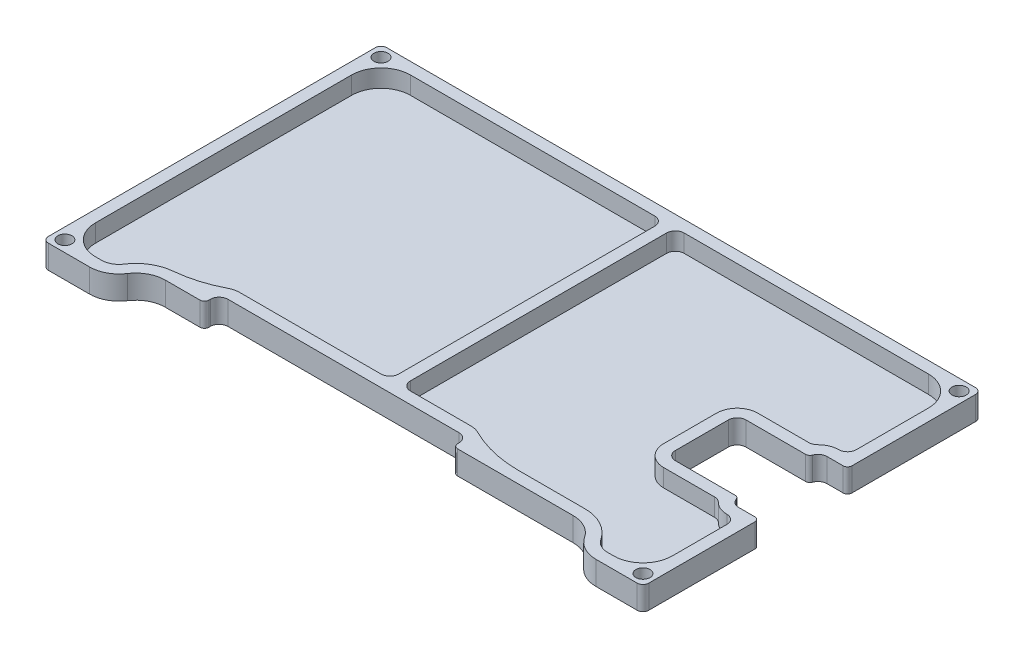
SolidWorks part; units mm, degrees
material "7075-T6 (SN)"
ref_plane "Ebene vorne" through (0, 0, 0) normal (0, 0, 1) x (1, 0, 0)
ref_plane "Ebene oben" through (0, 0, 0) normal (0, 1, 0) x (1, 0, 0)
ref_plane "Ebene rechts" through (0, 0, 0) normal (1, 0, 0) x (0, 0, -1)
sketch "Skizze1" plane through (0, 0, 0) normal (0, 1, 0) x (1, 0, 0)
  line L1 (-49.1, -26.85) -> (49.1, -26.85) construction
  line L2 (-49.1, -26.85) -> (-49.1, 26.85) construction
  line L3 (-49.1, 26.85) -> (49.1, 26.85) construction
  line L4 (49.1, -26.85) -> (49.1, 26.85) construction
  line L5 (-49.1, -26.85) -> (49.1, 26.85) construction
  line L6 (-49.1, 26.85) -> (49.1, -26.85) construction
  line L7 (-51, -28.75) -> (51, -28.75)
  line L8 (-51, -28.75) -> (-51, 28.75)
  line L9 (-51, 28.75) -> (51, 28.75)
  line L10 (51, -28.75) -> (51, 28.75)
  line L11 (-51, -28.75) -> (51, 28.75) construction
  line L12 (-51, 28.75) -> (51, -28.75) construction
  point P0 (0, 0)
  point P6 (0, 0)
  dimension "D1" = 102
  dimension "D2" = 57.5
  dimension "D3" = 98.2
  dimension "D4" = 53.7
extrude "Aufsatz-Linear austragen1" add sketch "Skizze1" along normal blind 1
fillet "Verrundung1" radius 1 4 edges at (51, 0.5, -28.75) (51, 0.5, 28.75) (-51, 0.5, 28.75) (-51, 0.5, -28.75)
sketch "Skizze5" plane through (0, 1, 0) normal (0, 1, 0) x (1, 0, 0)
  line L0 (-43, -28.75) -> (43, -28.75)
  line L1 (-50, -28.75) -> (50, -28.75) construction
  line L2 (-51, 27.75) -> (-51, -27.75) construction
  line L3 (34.6484, -24.25) -> (-34.6484, -24.25)
  line L4 (51, -27.75) -> (51, 27.75) construction
  arc A0 (-38.8242, -26.5) -> (-43, -28.75) centre (-43, -23.75) cw
  arc A1 (-38.8242, -26.5) -> (-34.6484, -24.25) centre (-34.6484, -29.25) cw
  arc A2 (38.8242, -26.5) -> (34.6484, -24.25) centre (34.6484, -29.25) ccw
  arc A3 (43, -28.75) -> (38.8242, -26.5) centre (43, -23.75) cw
  dimension "D3" = 5
  dimension "D1" = 8
  dimension "D2" = 8
  dimension "D4" = 4.5
extrude "Schnitt-Linear austragen1" cut sketch "Skizze5" against normal up to next
sketch "Skizze6" plane through (0, 1, 0) normal (0, 1, 0) x (1, 0, 0)
  line L0 (14.25, -21.75) -> (-28, -21.75)
  line L2 (-28, -21.75) -> (-28, -24.25)
  line L3 (-28, -24.25) -> (14.25, -24.25)
  line L4 (14.25, -24.25) -> (14.25, -21.75)
  line L5 (51, -27.75) -> (51, 27.75) construction
  line L7 (33.75, 4.5) -> (46, 4.5)
  line L8 (51, 4.5) -> (51, -7.5)
  line L9 (46, -7.5) -> (33.75, -7.5)
  line L10 (33.75, -7.5) -> (33.75, 4.5)
  line L11 (43, -28.75) -> (50, -28.75) construction
  line L12 (-51, 27.75) -> (-51, -27.75) construction
  line L13 (34.6484, -24.25) -> (-34.6484, -24.25) construction
  line L14 (46, -7.5) -> (46, -9)
  line L15 (46, -9) -> (51, -9)
  line L16 (51, -9) -> (51, -7.5)
  line L17 (46, 4.5) -> (46, 6)
  line L18 (46, 6) -> (51, 6)
  line L19 (51, 6) -> (51, 4.5)
  line L20 (46, -7.5) -> (51, -7.5) construction
  line L21 (46, 4.5) -> (51, 4.5) construction
  dimension "D1" = 42.25
  dimension "D2" = 23
  dimension "D3" = 2.5
  dimension "D4" = 21.25
  dimension "D5" = 12
  dimension "D6" = 17.25
  dimension "D7" = 15
  dimension "D8" = 5
extrude "Schnitt-Linear austragen2" cut sketch "Skizze6" against normal up to next
fillet "Verrundung2" radius 1.5 6 edges at (33.75, 0.5, -4.5) (33.75, 0.5, 7.5) (14.25, 0.5, 21.75) (-28, 0.5, 21.75) (46, 0.5, -6) (46, 0.5, 9)
fillet "Verrundung3" radius 0.75 6 edges at (-28, 0.5, 24.25) (14.25, 0.5, 24.25) (51, 0.5, -6) (51, 0.5, 9) (46, 0.5, -4.5) (46, 0.5, 7.5)
sketch "Skizze8" plane through (0, 1, 0) normal (0, 1, 0) x (1, 0, 0)
  line L0 (35.25, 6.5) -> (44.6277, 6.5)
  line L1 (47.5, 8) -> (49, 8)
  line L2 (49, 8) -> (49, 26.75)
  line L3 (49, 26.75) -> (1, 26.75)
  line L4 (-49, 26.75) -> (-49, -26.75)
  line L5 (-49, -26.75) -> (-43, -26.75)
  line L6 (-34.6484, -22.25) -> (-29.8541, -22.25)
  line L7 (-29.8541, -22.25) -> (-29.8541, -22.25)
  line L8 (-26.5, -19.75) -> (-1, -19.75)
  line L9 (16.1041, -22.25) -> (16.1041, -22.25)
  line L10 (16.1041, -22.25) -> (34.6484, -22.25)
  line L11 (43, -26.75) -> (49, -26.75)
  line L12 (49, -26.75) -> (49, -11)
  line L13 (49, -11) -> (47.5, -11)
  line L14 (44.6277, -9.5) -> (35.25, -9.5)
  line L15 (31.75, -6) -> (31.75, 3)
  line L16 (35.25, 4.5) -> (45.3787, 4.5)
  line L17 (47.5, 6) -> (50.25, 6)
  line L18 (51, 6.75) -> (51, 27.75)
  line L19 (50, 28.75) -> (-50, 28.75)
  line L20 (-51, 27.75) -> (-51, -27.75)
  line L21 (-50, -28.75) -> (-43, -28.75)
  line L22 (-34.6484, -24.25) -> (-28.75, -24.25)
  line L23 (-28, -23.5) -> (-28, -23.25)
  line L24 (-26.5, -21.75) -> (12.75, -21.75)
  line L25 (14.25, -23.25) -> (14.25, -23.5)
  line L26 (15, -24.25) -> (34.6484, -24.25)
  line L27 (43, -28.75) -> (50, -28.75)
  line L28 (51, -27.75) -> (51, -9.75)
  line L29 (50.25, -9) -> (47.5, -9)
  line L30 (45.3787, -7.5) -> (35.25, -7.5)
  line L31 (33.75, -6) -> (33.75, 3)
  line L32 (35.25, 4.5) -> (45.3787, 4.5)
  line L33 (47.5, 6) -> (50.25, 6)
  line L34 (51, 6.75) -> (51, 27.75)
  line L35 (50, 28.75) -> (-50, 28.75)
  line L36 (-51, 27.75) -> (-51, -27.75)
  line L37 (-50, -28.75) -> (-43, -28.75)
  line L38 (-34.6484, -24.25) -> (-28.75, -24.25)
  line L39 (-28, -23.5) -> (-28, -23.25)
  line L40 (-26.5, -21.75) -> (12.75, -21.75)
  line L41 (14.25, -23.25) -> (14.25, -23.5)
  line L42 (15, -24.25) -> (34.6484, -24.25)
  line L43 (43, -28.75) -> (50, -28.75)
  line L44 (51, -27.75) -> (51, -9.75)
  line L45 (50.25, -9) -> (47.5, -9)
  line L46 (45.3787, -7.5) -> (35.25, -7.5)
  line L47 (33.75, -6) -> (33.75, 3)
  line L48 (-1, 26.75) -> (-1, -19.75)
  line L49 (1, 0) -> (0, 0) construction
  line L50 (0, 0) -> (-1, 0) construction
  line L51 (1, 26.75) -> (1, -19.75)
  line L52 (1, -19.75) -> (12.75, -19.75)
  line L53 (-26.5, -19.75) -> (12.75, -19.75) construction
  line L54 (-1, 26.75) -> (-49, 26.75)
  line L55 (49, 26.75) -> (-49, 26.75) construction
  arc A0 (44.6277, 6.5) -> (44.6277, 6.5) centre (44.6277, 6.5) ccw
  arc A1 (47.5, 8) -> (44.6277, 6.5) centre (47.5, 4.5) ccw
  arc A2 (49, 8) -> (49, 8) centre (49, 8) ccw
  arc A3 (49, 26.75) -> (49, 26.75) centre (49, 26.75) ccw
  arc A4 (-49, 26.75) -> (-49, 26.75) centre (-49, 26.75) ccw
  arc A5 (-49, -26.75) -> (-49, -26.75) centre (-49, -26.75) ccw
  arc A6 (-43, -26.75) -> (-40.4945, -25.4) centre (-43, -23.75) ccw
  arc A7 (-34.6484, -22.25) -> (-40.4945, -25.4) centre (-34.6484, -29.25) ccw
  arc A8 (-29.8541, -22.25) -> (-29.8541, -22.25) centre (-29.8541, -22.25) ccw
  arc A9 (-26.5, -19.75) -> (-29.8541, -22.25) centre (-26.5, -23.25) ccw
  arc A10 (16.1041, -22.25) -> (12.75, -19.75) centre (12.75, -23.25) ccw
  arc A11 (16.1041, -22.25) -> (16.1041, -22.25) centre (16.1041, -22.25) ccw
  arc A12 (40.4945, -25.4) -> (34.6484, -22.25) centre (34.6484, -29.25) ccw
  arc A13 (40.4945, -25.4) -> (43, -26.75) centre (43, -23.75) ccw
  arc A14 (49, -26.75) -> (49, -26.75) centre (49, -26.75) ccw
  arc A15 (49, -11) -> (49, -11) centre (49, -11) ccw
  arc A16 (44.6277, -9.5) -> (47.5, -11) centre (47.5, -7.5) ccw
  arc A17 (44.6277, -9.5) -> (44.6277, -9.5) centre (44.6277, -9.5) ccw
  arc A18 (31.75, -6) -> (35.25, -9.5) centre (35.25, -6) ccw
  arc A19 (35.25, 6.5) -> (31.75, 3) centre (35.25, 3) ccw
  arc A20 (45.3787, 4.5) -> (46.0858, 5) centre (45.3787, 5.25) ccw
  arc A21 (47.5, 6) -> (46.0858, 5) centre (47.5, 4.5) ccw
  arc A22 (50.25, 6) -> (51, 6.75) centre (50.25, 6.75) ccw
  arc A23 (51, 27.75) -> (50, 28.75) centre (50, 27.75) ccw
  arc A24 (-50, 28.75) -> (-51, 27.75) centre (-50, 27.75) ccw
  arc A25 (-51, -27.75) -> (-50, -28.75) centre (-50, -27.75) ccw
  arc A26 (-43, -28.75) -> (-38.8242, -26.5) centre (-43, -23.75) ccw
  arc A27 (-34.6484, -24.25) -> (-38.8242, -26.5) centre (-34.6484, -29.25) ccw
  arc A28 (-28.75, -24.25) -> (-28, -23.5) centre (-28.75, -23.5) ccw
  arc A29 (-26.5, -21.75) -> (-28, -23.25) centre (-26.5, -23.25) ccw
  arc A30 (14.25, -23.25) -> (12.75, -21.75) centre (12.75, -23.25) ccw
  arc A31 (14.25, -23.5) -> (15, -24.25) centre (15, -23.5) ccw
  arc A32 (38.8242, -26.5) -> (34.6484, -24.25) centre (34.6484, -29.25) ccw
  arc A33 (38.8242, -26.5) -> (43, -28.75) centre (43, -23.75) ccw
  arc A34 (50, -28.75) -> (51, -27.75) centre (50, -27.75) ccw
  arc A35 (51, -9.75) -> (50.25, -9) centre (50.25, -9.75) ccw
  arc A36 (46.0858, -8) -> (47.5, -9) centre (47.5, -7.5) ccw
  arc A37 (46.0858, -8) -> (45.3787, -7.5) centre (45.3787, -8.25) ccw
  arc A38 (33.75, -6) -> (35.25, -7.5) centre (35.25, -6) ccw
  arc A39 (35.25, 4.5) -> (33.75, 3) centre (35.25, 3) ccw
  arc A40 (45.3787, 4.5) -> (46.0858, 5) centre (45.3787, 5.25) ccw
  arc A41 (47.5, 6) -> (46.0858, 5) centre (47.5, 4.5) ccw
  arc A42 (50.25, 6) -> (51, 6.75) centre (50.25, 6.75) ccw
  arc A43 (51, 27.75) -> (50, 28.75) centre (50, 27.75) ccw
  arc A44 (-50, 28.75) -> (-51, 27.75) centre (-50, 27.75) ccw
  arc A45 (-51, -27.75) -> (-50, -28.75) centre (-50, -27.75) ccw
  arc A46 (-43, -28.75) -> (-38.8242, -26.5) centre (-43, -23.75) ccw
  arc A47 (-34.6484, -24.25) -> (-38.8242, -26.5) centre (-34.6484, -29.25) ccw
  arc A48 (-28.75, -24.25) -> (-28, -23.5) centre (-28.75, -23.5) ccw
  arc A49 (-26.5, -21.75) -> (-28, -23.25) centre (-26.5, -23.25) ccw
  arc A50 (14.25, -23.25) -> (12.75, -21.75) centre (12.75, -23.25) ccw
  arc A51 (14.25, -23.5) -> (15, -24.25) centre (15, -23.5) ccw
  arc A52 (38.8242, -26.5) -> (34.6484, -24.25) centre (34.6484, -29.25) ccw
  arc A53 (38.8242, -26.5) -> (43, -28.75) centre (43, -23.75) ccw
  arc A54 (50, -28.75) -> (51, -27.75) centre (50, -27.75) ccw
  arc A55 (51, -9.75) -> (50.25, -9) centre (50.25, -9.75) ccw
  arc A56 (46.0858, -8) -> (47.5, -9) centre (47.5, -7.5) ccw
  arc A57 (46.0858, -8) -> (45.3787, -7.5) centre (45.3787, -8.25) ccw
  arc A58 (33.75, -6) -> (35.25, -7.5) centre (35.25, -6) ccw
  arc A59 (35.25, 4.5) -> (33.75, 3) centre (35.25, 3) ccw
  dimension "D3" = 2
  dimension "D1" = 0
  dimension "D2" = 2
extrude "Aufsatz-Linear austragen2" add sketch "Skizze8" along normal blind 3
fillet "Verrundung4" radius 5 4 edges at (49, 2.5, -26.75) (49, 2.5, 26.75) (-49, 2.5, 26.75) (-49, 2.5, -26.75)
hole_wizard "Durchgangsloch für M21" positions "Skizze4" profile "Skizze2" hole size "M2" standard "DIN" end condition up to next
sketch "Skizze4" plane through (0, 0, 0) normal (0, -1, 0) x (-1, 0, 0)
  line L1 (49.1, 26.85) -> (-49.1, 26.85)
  line L2 (49.1, 26.85) -> (49.1, -26.85)
  line L3 (49.1, -26.85) -> (-49.1, -26.85)
  line L4 (-49.1, 26.85) -> (-49.1, -26.85)
  line L5 (49.1, 26.85) -> (-49.1, -26.85) construction
  line L6 (49.1, -26.85) -> (-49.1, 26.85) construction
  point P2 (-49.1, -26.85)
  point P107 (49.1, 26.85)
  point P108 (49.1, -26.85)
  point P109 (-49.1, 26.85)
  dimension "D1" = 98.2
  dimension "D2" = 53.7
sketch "Skizze2" plane through (49.1, 0, 26.85) normal (1, 0, 0) x (0, 0, -1)
  line L0 (0, 0) -> (0, 4)
  line L1 (0, 4) -> (1.2, 4)
  line L2 (1.2, 4) -> (1.2, 0)
  line L5 (1.2, 0) -> (0, 0)
  line L11 (0, -6.35) -> (0, 107.95) construction
  dimension "Bohrerdurchmesser" = 2.4
  dimension "Bohrungstiefe" = 4
fillet "Verrundung5" radius 1.5 8 edges at (-1, 2.5, -26.75) (-1, 2.5, 19.75) (1, 2.5, 19.75) (1, 2.5, -26.75) (49, 2.5, -8) (44.6277, 2.5, -6.5) (44.6277, 2.5, 9.5) (49, 2.5, 11)
fillet "Verrundung6" radius 20 2 edges at (16.1041, 2.5, 22.25) (-29.8541, 2.5, 22.25)
